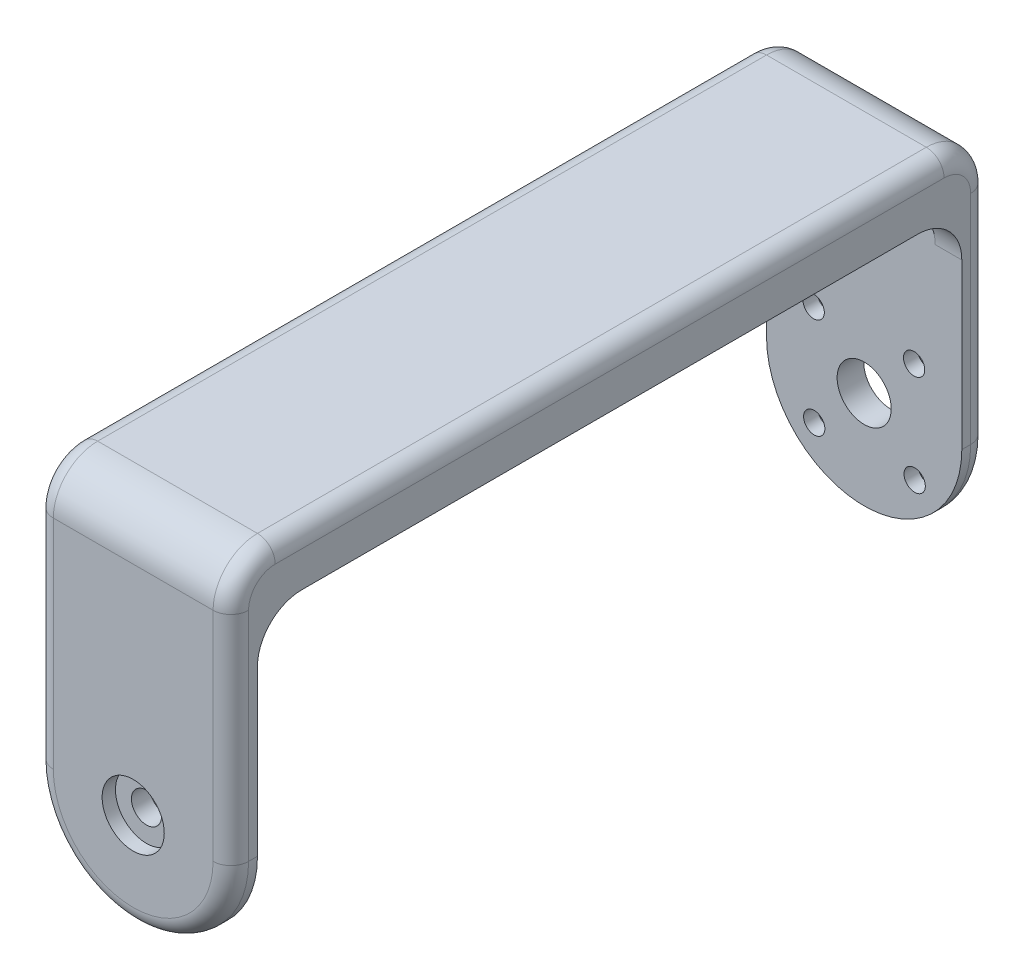
SolidWorks part; units mm, degrees
ref_plane "Plano frontal" through (0, 0, 0) normal (0, 0, 1) x (1, 0, 0)
ref_plane "Plano superior" through (0, 0, 0) normal (0, 1, 0) x (1, 0, 0)
ref_plane "Plano direito" through (0, 0, 0) normal (1, 0, 0) x (0, 0, -1)
sketch "Esboço1" plane through (0, 0, 0) normal (0, 0, 1) x (1, 0, 0)
  line L0 (11, -1.4281) -> (11, 25.0719)
  line L1 (11, 25.0719) -> (-11, 25.0719)
  line L2 (-11, 25.0719) -> (-11, -1.4281)
  line L4 (11, -3.4281) -> (11, 5.0719) construction
  line L5 (7.3, 10.0719) -> (-7.3, 10.0719) construction
  circle A3 centre (0, -1.4281) radius 11 construction
  arc A8 (-11, -1.4281) -> (11, -1.4281) centre (0, -1.4281) ccw
  circle A9 centre (0, -1.4281) radius 3.05 construction
  circle A10 centre (0, -1.4281) radius 3.05
  dimension "D1" = 15
extrude "Ressalto-extrusão1" add sketch "Esboço1" against normal blind 3
sketch "Esboço2" plane through (0, 25.0719, 0) normal (0, 1, 0) x (1, 0, 0)
  line L0 (-3.85, -78.5) -> (3.85, -78.5) construction
  line L1 (-11, 3) -> (11, 3)
  line L2 (-11, 3) -> (-11, -79.35)
  line L3 (-11, -79.35) -> (11, -79.35)
  line L4 (11, 3) -> (11, -79.35)
  dimension "D1" = 0.85
extrude "Ressalto-extrusão2" add sketch "Esboço2" along normal blind 3
sketch "Esboço3" plane through (0, 0, 79.35) normal (0, 0, 1) x (1, 0, 0)
  line L0 (11, 28.0719) -> (-11, 28.0719)
  line L1 (-11, 28.0719) -> (-11, -1.4281)
  line L2 (11, -1.4281) -> (11, 28.0719)
  arc A0 (-11, -1.4281) -> (11, -1.4281) centre (0, -1.4281) ccw
  circle A3 centre (0, -1.4281) radius 4 construction
extrude "Ressalto-extrusão3" add sketch "Esboço3" along normal blind 3
sketch "Esboço6" plane through (11, 0, 0) normal (1, 0, 0) x (0, 0, -1)
  line L0 (3, -1.4281) -> (3, 28.0719) construction
  line L1 (-82.35, 28.0719) -> (3, 28.0719)
  line L2 (-82.35, 28.0719) -> (-82.35, 22.0719)
  line L3 (-82.35, 22.0719) -> (3, 22.0719)
  line L4 (3, 28.0719) -> (3, 22.0719)
  line L5 (-79.35, 25.0719) -> (0, 25.0719) construction
  dimension "D1" = 3
extrude "Ressalto-extrusão5" add sketch "Esboço6" against normal blind 3
mirror "Espelhar1" about plane through (0, 0, 0) normal (1, 0, 0) of "Ressalto-extrusão5"
sketch "Esboço7" plane through (0, 0, 79.35) normal (0, 0, -1) x (-1, 0, 0)
  circle A0 centre (0, -1.4281) radius 2.75
  circle A2 centre (0, -1.4281) radius 3.25 construction
  dimension "D1" = 0.5
extrude "Ressalto-extrusão6" add sketch "Esboço7" along normal offset from surface (0.6 mm away) 0.25
hole_wizard "Rebaixo para parafuso com cabeça panela de M31" positions "Esboço8" profile "Esboço9" counterbore size "M3" standard "DIN" end condition up to next
sketch "Esboço8" plane through (0, 0, 82.35) normal (0, 0, 1) x (1, 0, 0)
  circle A0 centre (0, -1.4281) radius 3.25 construction
  point P0 (0, -1.4281)
sketch "Esboço9" plane through (0, -1.4281, 82.35) normal (1, 0, 0) x (0, -1, 0)
  line L0 (0, 0) -> (0, 3.6)
  line L1 (0, 3.6) -> (1.7, 3.6)
  line L3 (1.7, 3.6) -> (1.7, 1.5)
  line L4 (1.7, 1.5) -> (3.5, 1.5)
  line L5 (3.5, 1.5) -> (3.5, 0)
  line L7 (3.5, 0) -> (0, 0)
  line L11 (0, -6.35) -> (0, 107.95) construction
  dimension "Thru Hole Dia." = 3.4
  dimension "Thru Hole Depth" = 3.6
  dimension "C'Bore Dia." = 7
  dimension "C'Bore Depth" = 1.5
hole_wizard "Rebaixo para parafuso com cabeça redonda de M21" positions "Esboço10" profile "Esboço11" counterbore size "M2" standard "DIN" end condition up to next
sketch "Esboço10" plane through (0, 0, -3) normal (0, 0, -1) x (-1, 0, 0)
  circle A0 centre (-5.6247, 4.2606) radius 1.025 construction
  point P0 (-5.6247, 4.2606)
sketch "Esboço11" plane through (5.6247, 4.2606, -3) normal (1, 0, 0) x (0, 1, 0)
  line L0 (0, 0) -> (0, 3)
  line L1 (0, 3) -> (1.2, 3)
  line L3 (1.2, 3) -> (1.2, 1.4)
  line L4 (1.2, 1.4) -> (2.2, 1.4)
  line L5 (2.2, 1.4) -> (2.2, 0)
  line L7 (2.2, 0) -> (0, 0)
  line L11 (0, -6.35) -> (0, 107.95) construction
  dimension "Thru Hole Dia." = 2.4
  dimension "Thru Hole Depth" = 3
  dimension "C'Bore Dia." = 4.4
  dimension "C'Bore Depth" = 1.4
pattern_circular "PadrãoCircular1" count 4 over 360 about axis through (0, -1.4281, -3) along (0, 0, 1) of "Rebaixo para parafuso com cabeça redonda de M21"
fillet "Filete1" radius 5 4 edges at (0, 25.0719, 0) (0, 25.0719, 79.35) (0, 28.0719, -3) (0, 28.0719, 82.35)
fillet "Filete2" radius 5 4 edges at (9.5, 22.0719, 0.4174) (-9.5, 22.0719, 0.4174) (9.5, 22.0719, 78.9326) (-9.5, 22.0719, 78.9326)
fillet "Filete3" radius 2 12 edges at (-11, 26.6074, -1.5355) (-11, 10.8219, -3) (0, -12.4281, -3) (11, 10.8219, -3) (11, 26.6074, -1.5355) (11, 26.6074, 80.8855) (11, 10.8219, 82.35) (0, -12.4281, 82.35) (-11, 10.8219, 82.35) (-11, 26.6074, 80.8855) (11, 28.0719, 39.675) (-11, 28.0719, 39.675)
